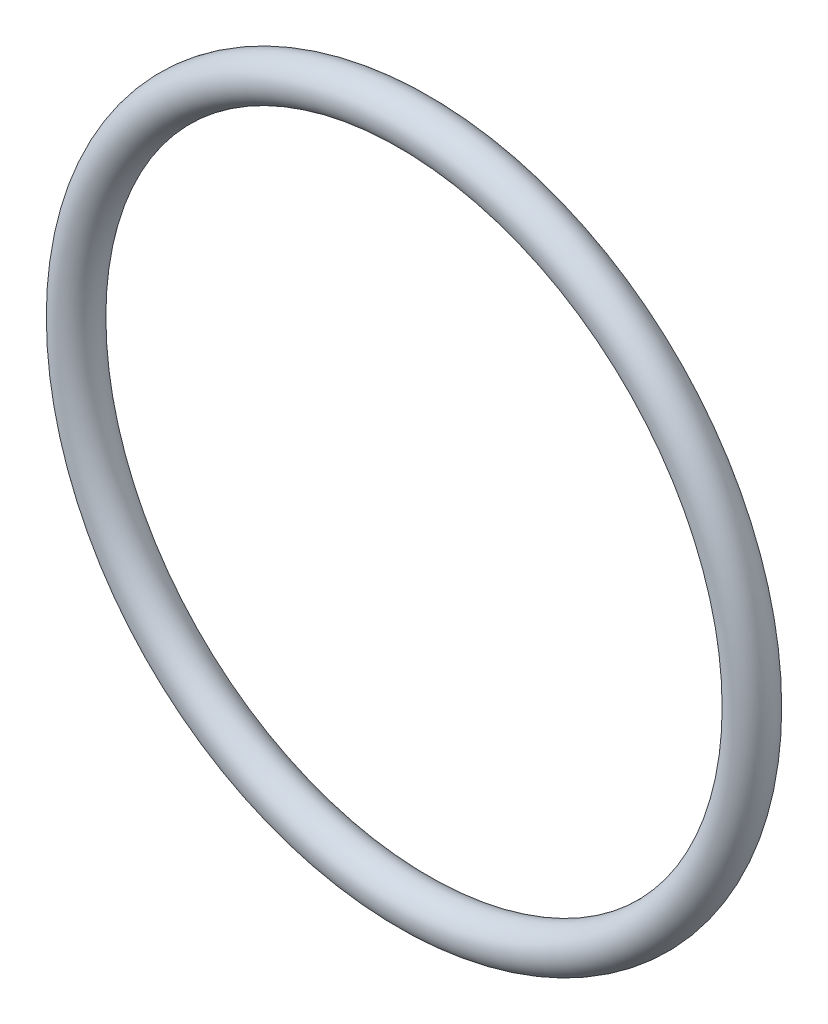
SolidWorks part; units mm, degrees
material "Rubber"
ref_plane "Front" through (0, 0, 0) normal (0, 0, 1) x (1, 0, 0)
ref_plane "Top" through (0, 0, 0) normal (0, 1, 0) x (1, 0, 0)
ref_plane "Right" through (0, 0, 0) normal (1, 0, 0) x (0, 0, -1)
sketch "Sketch1" plane through (0, 0, 0) normal (1, 0, 0) x (0, -1, 0)
  line L0 (0, -1.3081) -> (0, 1.3081) construction
  line L2 (-24.5174, 0) -> (24.5174, 0) construction
  line L3 (-19.6723, 0) -> (19.6723, 0) construction
  circle A0 centre (20.9804, 0) radius 1.3081
  point P9 (19.6723, 0)
  point P10 (22.2885, 0)
  point P13 (20.9804, 1.3081)
  point P14 (20.9804, -1.3081)
  dimension "Width" = 2.6162
  dimension "ID" = 39.3446
revolve "Revolve1" add sketch "Sketch1" angle 360 about L0
ref_axis "Axis1" through (0, 0, 0) along (0, 0, 1)
